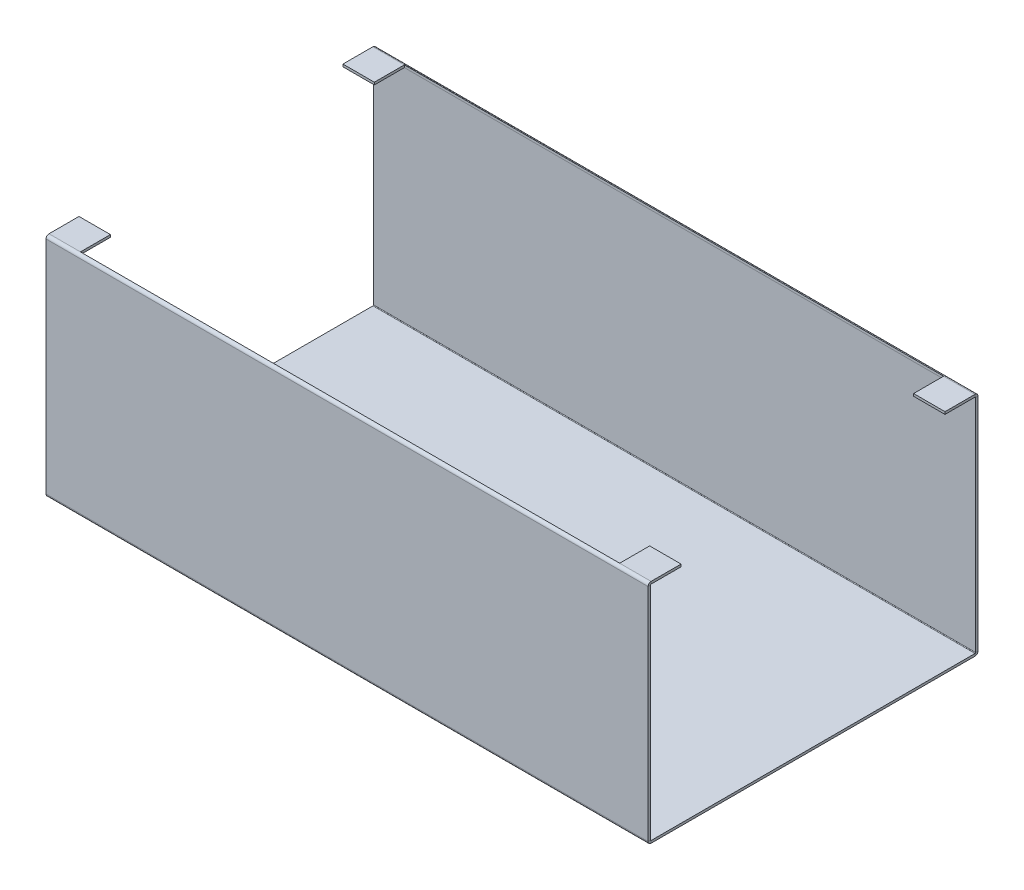
SolidWorks part; units mm, degrees
note: The reader was unsure of these and kept them because the rebuilt part matched: flange length of "Brida de arista1", "Brida de arista2".
ref_plane "Alzado" through (0, 0, 0) normal (0, 0, 1) x (1, 0, 0)
ref_plane "Planta" through (0, 0, 0) normal (0, 1, 0) x (1, 0, 0)
ref_plane "Vista lateral" through (0, 0, 0) normal (1, 0, 0) x (0, 0, -1)
sketch "Croquis1" plane through (0, 0, 0) normal (0, 1, 0) x (1, 0, 0)
  line L1 (-365, -200) -> (365, -200)
  line L2 (-365, -200) -> (-365, 200)
  line L3 (-365, 200) -> (365, 200)
  line L4 (365, -200) -> (365, 200)
  line L5 (-365, -200) -> (365, 200) construction
  line L6 (-365, 200) -> (365, -200) construction
  point P0 (0, 0)
  dimension "D1" = 730
  dimension "D2" = 400
base flange "Brida base1" sketch "Croquis1" thickness 2.9 reverse thickness direction no parameters "D1"=0.7366
edge flange "Brida de arista1" sketch "Croquis10" flange profiles "Croquis10", "Croquis11" flange angle 90 flange length 275 flange position material inside bend radius 0.7366 thickness 2.9 relief rectangular parameters "D6"=10, "D8"=0.5
sketch "Croquis10" plane through (0, 0, -200) normal (0, 0, -1) x (-1, 0, 0)
  line L0 (-365, 0) -> (365, 0) construction
  line L1 (-365, 0) -> (365, 0)
  line L2 (-365, 0) -> (-365, 272.1)
  line L3 (-365, 272.1) -> (365, 272.1)
  line L4 (365, 272.1) -> (365, 0)
sketch "Croquis11" plane through (0, 0, 200) normal (0, 0, 1) x (1, 0, 0)
  line L0 (-365, 0) -> (365, 0) construction
  line L1 (-365, 0) -> (365, 0)
  line L2 (-365, 0) -> (-365, 272.1)
  line L3 (-365, 272.1) -> (365, 272.1)
  line L4 (365, 272.1) -> (365, 0)
bend "Pliegue de arista1" bend radius 0.7366 bend angle 90 parameters "D5"=1
bend "Pliegue de arista2" bend radius 0.7366 bend angle 90 parameters "D5"=2
edge flange "Brida de arista2" sketch "Croquis16" flange profiles "Croquis16", "Croquis17" flange angle 90 flange length 40 flange position material inside bend radius 0.7366 thickness 2.9 relief rectangular parameters "D6"=10, "D8"=0.5
sketch "Croquis16" plane through (0, 272.1, -197.1) normal (0, 1, 0) x (-1, 0, 0)
  line L2 (-365, 0) -> (-365, 37.1)
  line L3 (-365, 37.1) -> (365, 37.1)
  line L4 (365, 37.1) -> (365, 0)
  line L7 (365, 0) -> (-365, 0) construction
  line L8 (365, 0) -> (-365, 0)
sketch "Croquis17" plane through (0, 272.1, 197.1) normal (0, 1, 0) x (1, 0, 0)
  line L0 (365, 0) -> (-365, 0) construction
  line L1 (365, 0) -> (-365, 0)
  line L2 (-365, 0) -> (-365, 37.1)
  line L3 (-365, 37.1) -> (365, 37.1)
  line L4 (365, 37.1) -> (365, 0)
bend "Pliegue de arista3" bend radius 0.7366 bend angle 90 parameters "D5"=3
bend "Pliegue de arista4" bend radius 0.7366 bend angle 90 parameters "D5"=4
sketch "Croquis18" plane through (0, 272.1, 0) normal (0, 1, 0) x (1, 0, 0)
  line L0 (365, -160) -> (-365, -160) construction
  line L1 (-326.9, -160) -> (326.9, -160)
  line L2 (-326.9, -160) -> (-326.9, -196.3634)
  line L3 (-326.9, -196.3634) -> (326.9, -196.3634)
  line L4 (326.9, -160) -> (326.9, -196.3634)
  line L5 (365, -196.3634) -> (-365, -196.3634) construction
  line L6 (365, -196.3634) -> (365, -160) construction
  line L7 (-365, -160) -> (-365, -196.3634) construction
  line L8 (365, 0) -> (0, 0) construction
  line L9 (365, -196.3634) -> (365, 196.3634) construction
  line L10 (326.9, 160) -> (326.9, 196.3634)
  line L11 (-326.9, 196.3634) -> (326.9, 196.3634)
  line L12 (-326.9, 160) -> (-326.9, 196.3634)
  line L13 (-326.9, 160) -> (326.9, 160)
  dimension "D1" = 38.1
  dimension "D2" = 38.1
extrude "Cortar-Extruir1" cut sketch "Croquis18" against normal blind 4 normal cut yes
sketch "Líneas de pliegue1" [suppressed] plane through (0, 0, 0) normal (0, 1, 0) x (1, 0, 0)
sketch "Cuadro delimitador1" [suppressed] plane through (0, 0, 0) normal (0, 1, 0) x (1, 0, 0)
sheet metal parameters "Chapa metálica1" thickness 2.9 parameters "D1"=0.7366
flat pattern "Chapa desplegada1" [suppressed]
sketch "Líneas de pliegue2" plane through (0, 0, 0) normal (0, 1, 0) x (1, 0, 0)
sketch3d "Cuadro delimitador2" [suppressed]
  line L0 (350, 175, 0) -> (-350, 175, 0) construction
  line L1 (350, -175, 0) -> (-350, -175, 0) construction
  line L2 (350, 175, 0) -> (350, -175, 0) construction
  line L3 (-350, 175, 0) -> (-350, -175, 0) construction
sheet metal parameters "Chapa metálica2" thickness 2.9 parameters "D1"=0.7366
flat pattern "Chapa desplegada1"
sketch "Líneas de pliegue2" plane through (0, 0, 0) normal (0, 1, 0) x (1, 0, 0)
  line L0 (-360, -173.0808) -> (360, -173.0808) construction
  line L1 (360, 173.0808) -> (-360, 173.0808) construction
  line L2 (-360, -173.0808) -> (360, -173.0808) construction
  line L3 (360, 173.0808) -> (-360, 173.0808) construction
sketch3d "Cuadro delimitador2" [suppressed]
  line L0 (-360, -446.1615, 0) -> (-360, 446.1615, 0) construction
  line L1 (360, -446.1615, 0) -> (360, 446.1615, 0) construction
  line L2 (-360, -446.1615, 0) -> (360, -446.1615, 0) construction
  line L3 (-360, 446.1615, 0) -> (360, 446.1615, 0) construction
bend of the flat pattern "Aplanar-<Pliegue de arista1>1"
bend of the flat pattern "Aplanar-<Pliegue de arista2>1"
sheet metal parameters "Chapa metálica3" thickness 2.9 parameters "D1"=0.7366
flat pattern "Chapa desplegada1"
sketch "Líneas de pliegue2" plane through (0, 0, 0) normal (0, 1, 0) x (1, 0, 0)
  line L0 (-365, -173.0808) -> (365, -173.0808) construction
  line L1 (365, 173.0808) -> (-365, 173.0808) construction
  line L2 (-365, -173.0808) -> (365, -173.0808) construction
  line L3 (365, 173.0808) -> (-365, 173.0808) construction
  line L4 (-365, -444.2423) -> (365, -444.2423) construction
  line L5 (365, 444.2423) -> (-365, 444.2423) construction
  line L6 (-365, -444.2423) -> (365, -444.2423) construction
  line L7 (365, 444.2423) -> (-365, 444.2423) construction
sketch3d "Cuadro delimitador2" [suppressed]
  line L0 (-365, -480.423, 0) -> (-365, 480.423, 0) construction
  line L1 (365, -480.423, 0) -> (365, 480.423, 0) construction
  line L2 (-365, -480.423, 0) -> (365, -480.423, 0) construction
  line L3 (-365, 480.423, 0) -> (365, 480.423, 0) construction
bend of the flat pattern "Aplanar-<Pliegue de arista1>1"
bend of the flat pattern "Aplanar-<Pliegue de arista2>1"
bend of the flat pattern "Aplanar-<Pliegue de arista3>1"
bend of the flat pattern "Aplanar-<Pliegue de arista4>1"
sheet metal parameters "Chapa metálica4" thickness 2.9 parameters "D1"=0.7366
flat pattern "Chapa desplegada1"
sketch "Líneas de pliegue2" plane through (0, 0, 0) normal (0, 1, 0) x (1, 0, 0)
  line L0 (-365, -198.0808) -> (365, -198.0808) construction
  line L1 (365, 198.0808) -> (-365, 198.0808) construction
  line L2 (-365, -198.0808) -> (365, -198.0808) construction
  line L3 (365, 198.0808) -> (-365, 198.0808) construction
  line L4 (-365, -469.2423) -> (365, -469.2423) construction
  line L5 (365, 469.2423) -> (-365, 469.2423) construction
  line L6 (-365, -469.2423) -> (365, -469.2423) construction
  line L7 (365, 469.2423) -> (-365, 469.2423) construction
sketch3d "Cuadro delimitador2" [suppressed]
  line L0 (-365, -507.323, 0) -> (-365, 507.323, 0) construction
  line L1 (365, -507.323, 0) -> (365, 507.323, 0) construction
  line L2 (-365, -507.323, 0) -> (365, -507.323, 0) construction
  line L3 (-365, 507.323, 0) -> (365, 507.323, 0) construction
bend of the flat pattern "Aplanar-<Pliegue de arista1>1"
bend of the flat pattern "Aplanar-<Pliegue de arista2>1"
bend of the flat pattern "Aplanar-<Pliegue de arista3>1"
bend of the flat pattern "Aplanar-<Pliegue de arista4>1"
